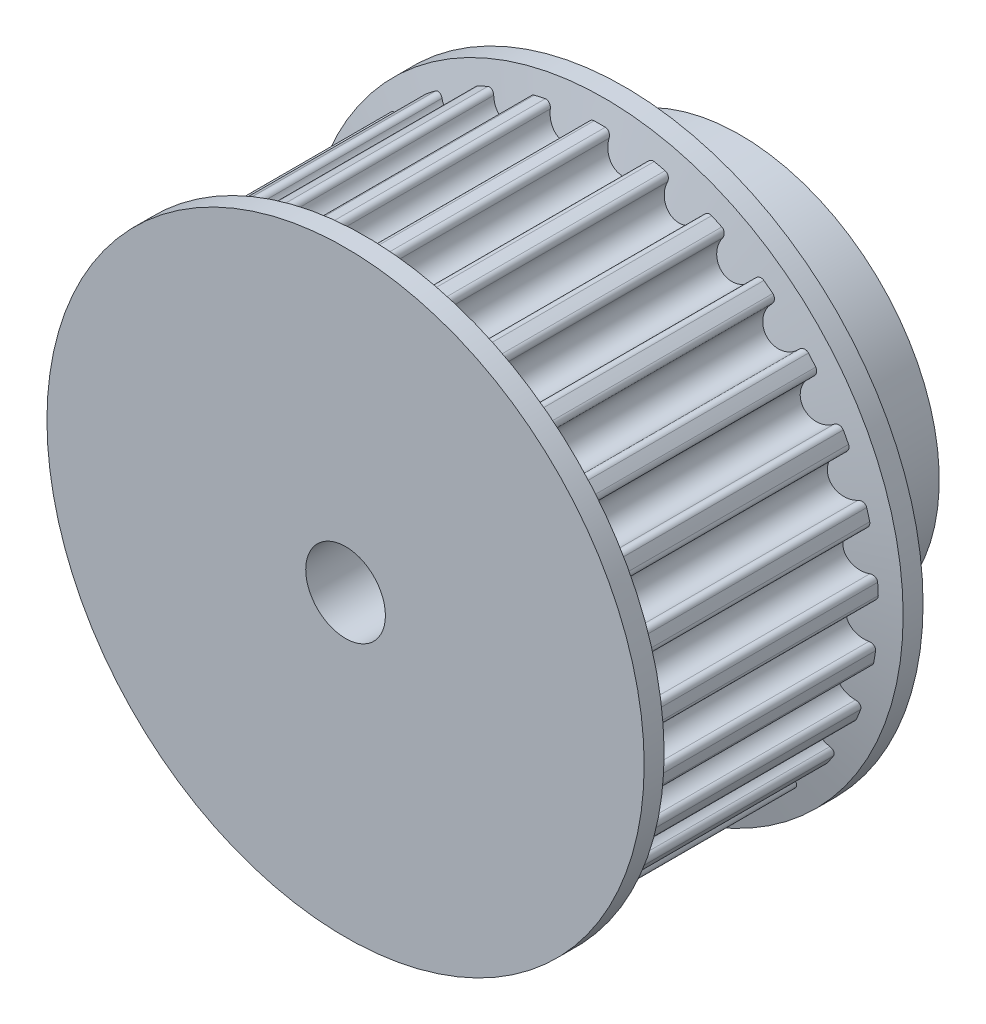
SolidWorks part; units mm, degrees
ref_plane "Front Plane" through (0, 0, 0) normal (0, 0, 1) x (1, 0, 0)
ref_plane "Top Plane" through (0, 0, 0) normal (0, 1, 0) x (1, 0, 0)
ref_plane "Right Plane" through (0, 0, 0) normal (1, 0, 0) x (0, 0, -1)
sketch "Sketch1" plane through (0, 0, 0) normal (0, 0, 1) x (1, 0, 0)
  circle A0 centre (0, 0) radius 23.0775
  dimension "D1" = 46.1549
extrude "Boss-Extrude1" add sketch "Sketch1" along normal mid plane 19.05
sketch "Sketch2" plane through (0, 0, 0) normal (0, 0, 1) x (1, 0, 0)
  line L0 (0, 0) -> (0, 22.2075) construction
  line L1 (0, 0) -> (2.3394, 21.5106) construction
  line L2 (0, 22.2075) -> (0, 23.0775)
  line L3 (2.3394, 21.5106) -> (2.4951, 22.9422) construction
  line L4 (4.7739, 21.6883) -> (4.961, 22.5379)
  arc A0 (0, 22.2075) -> (0.4461, 22.203) centre (0, 0) cw
  arc A1 (0.4461, 22.203) -> (0.8634, 21.7143) centre (0.4375, 21.7731) cw
  arc A2 (0.8634, 21.7143) -> (3.8247, 21.3922) centre (2.3394, 21.5106) ccw
  circle A3 centre (0, 0) radius 23.0775 construction
  arc A4 (0, 23.0775) -> (4.961, 22.5379) centre (0, 0) cw
  arc A5 (4.3373, 21.7798) -> (3.8247, 21.3922) centre (4.2533, 21.3581) ccw
  arc A6 (4.7739, 21.6883) -> (4.3373, 21.7798) centre (0, 0) ccw
  point P6 (2.1783, 20.0294)
  dimension "D1" = 0.43
  dimension "D2" = 1.49
  dimension "D3" = 0.87
  dimension "D4" = 6.207
  dimension "D5" = 2.93
extrude "Cut-Extrude1" cut sketch "Sketch2" against normal through all both and the other way through all
pattern_circular "CirPattern1" count 29 over 360 about axis through (0, 0, 9.525) along (0, 0, -1) of "Cut-Extrude1" reverse direction yes
sketch "Sketch4" plane through (0, 0, 9.525) normal (0, 0, 1) x (1, 0, 0)
  circle A0 centre (0, 0) radius 23.795
  arc A1 (20.4609, -8.6326) -> (20.7912, -7.8038) centre (0, 0) ccw construction
  circle A2 centre (0, 0) radius 3.175
  dimension "D1" = 1.5875
  dimension "D2" = 6.35
extrude "Boss-Extrude2" add sketch "Sketch4" along normal blind 1.5875
sketch "Sketch3" plane through (0, 0, 11.1125) normal (0, 0, 1) x (1, 0, 0)
  circle A0 centre (0, 0) radius 3.175
  dimension "D1" = 6.35
extrude "Cut-Extrude2" cut sketch "Sketch3" against normal through all both and the other way through all
sketch "Sketch6" plane through (0, 0, 0) normal (0, 1, 0) x (1, 0, 0)
  line L0 (23.795, -9.525) -> (18.542, -8.255)
  line L1 (18.542, -8.255) -> (18.542, -9.525)
  line L2 (19.8525, -9.525) -> (17.627, -9.525) construction
  line L3 (18.542, -9.525) -> (23.795, -9.525)
  dimension "D1" = 18.542
  dimension "D2" = 1.27
ref_axis "Axis1" through (0, 0, -9.525) along (0, 0, 1)
revolve "Revolve1" add sketch "Sketch6" angle 360 about axis through (0, 0, -9.525) along (0, 0, 1)
mirror "Mirror1" about plane through (0, 0, 0) normal (0, 0, 1) of "Boss-Extrude2", "Revolve1"
sketch "Sketch8" plane through (0, 0, -11.1125) normal (0, 0, -1) x (-1, 0, 0)
  circle A0 centre (0, 0) radius 15.875
  circle A1 centre (0, 0) radius 3.175 construction
  circle A2 centre (0, 0) radius 3.175
  dimension "D1" = 31.75
extrude "Boss-Extrude3" add sketch "Sketch8" along normal blind 9.2075
sketch "Sketch9" plane through (0, 0, -20.32) normal (0, 0, -1) x (-1, 0, 0)
  line L0 (0, -3.175) -> (0, -11.43) construction
  line L1 (0, -11.43) -> (-4.7625, -11.43) construction
  line L2 (0, -11.43) -> (4.7625, -11.43) construction
  line L4 (4.7625, -5.08) -> (-4.7625, -5.08)
  line L5 (4.7625, -5.08) -> (4.7625, -11.43)
  line L6 (4.7625, -11.43) -> (-4.7625, -11.43)
  line L7 (-4.7625, -5.08) -> (-4.7625, -11.43)
  line L8 (4.7625, -5.08) -> (-4.7625, -11.43) construction
  line L9 (4.7625, -11.43) -> (-4.7625, -5.08) construction
  circle A0 centre (0, 0) radius 3.175 construction
  point P9 (0, -8.255)
  dimension "D1" = 6.35
  dimension "D2" = 9.525
  dimension "D3" = 8.255
ref_plane "Plane1" through (0, -5.08, 0) normal (0, -1, 0) x (1, 0, 0)
sketch "Sketch10" plane through (0, -5.08, 0) normal (0, -1, 0) x (1, 0, 0)
  line L0 (0, -20.32) -> (0, -16.7005) construction
  line L1 (-23.795, -11.1125) -> (23.795, -11.1125) construction
  line L2 (-2.3464, -20.7645) -> (2.3464, -20.7645) construction
  line L3 (2.3464, -20.7645) -> (4.6927, -16.7005) construction
  line L4 (4.6927, -16.7005) -> (2.3464, -12.6365)
  line L5 (2.3464, -12.6365) -> (-2.3464, -12.6365)
  line L6 (-2.3464, -12.6365) -> (-4.6927, -16.7005)
  line L7 (-4.6927, -16.7005) -> (-2.3464, -20.7645) construction
  line L8 (4.6927, -16.7005) -> (4.6927, -23.9395)
  line L9 (4.6927, -23.9395) -> (-4.6927, -23.9395)
  line L10 (-4.6927, -23.9395) -> (-4.6927, -16.7005)
  line L11 (-15.875, -20.32) -> (15.875, -20.32) construction
  circle A0 centre (0, -16.7005) radius 4.064 construction
  circle A1 centre (0, -16.7005) radius 2.54
  circle A2 centre (0, -16.7005) radius 5.588 construction
  dimension "D2" = 5.08
  dimension "D3" = 3.6195
  dimension "D1" = 8.128
  dimension "D4" = 3.175
extrude "Cut-Extrude3" cut sketch "Sketch10" along normal up to vertex (6.35 mm away) contours L5 L6 L10 L9 L8 L4 up to point (4.7625, -11.43, -20.32)
extrude "Cut-Extrude4" cut sketch "Sketch10<3>" against normal blind 4.572 and the other way through all contours A1
sketch "Sketch10<3>" plane through (0, -5.08, 0) normal (0, -1, 0) x (1, 0, 0) same geometry as "Sketch10"
equation "\"n\"= 29'Number of Teeth"
equation "\"p\"= 5mm'Pitch"
equation "\"pd\"= \"n\" * \"p\" / pi'Pitch Diameter"
equation "\"D1@Sketch1\"=\"pd\""
equation "\"w\"= 0.75'Pulley Width"
equation "\"D1@Boss-Extrude1\"=\"w\""
equation "\"D4@Sketch2\"=180/\"n\""
equation "\"D1@CirPattern1\"=\"n\""
